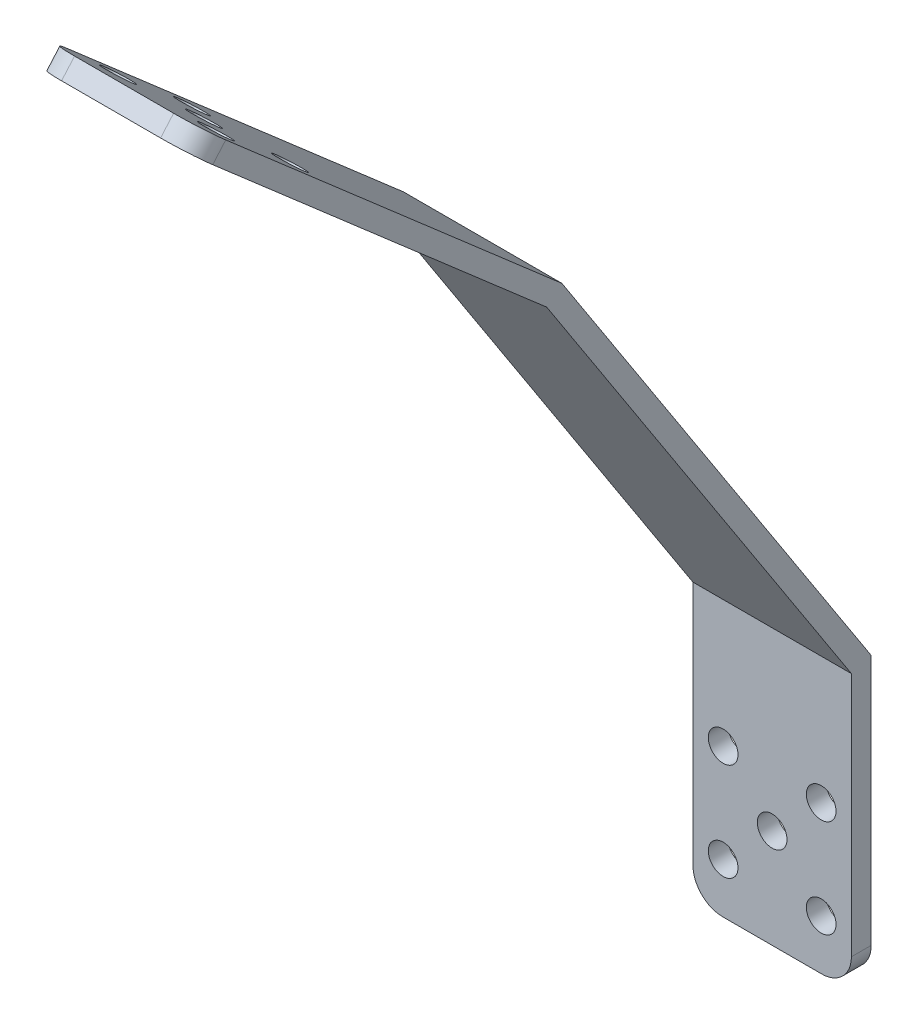
SolidWorks part; units mm, degrees
ref_plane "前视" through (0, 0, 0) normal (0, 0, 1) x (1, 0, 0)
ref_plane "上视" through (0, 0, 0) normal (0, 1, 0) x (1, 0, 0)
ref_plane "右视" through (0, 0, 0) normal (1, 0, 0) x (0, 0, -1)
sketch "草图1" plane through (0, 0, 0) normal (0, 0, 1) x (1, 0, 0)
  line L0 (0, 14.7362) -> (0, -14.2678) construction
  line L1 (-15.916, 0) -> (15.5486, 0) construction
  line L3 (-8, 24) -> (8, 24)
  line L4 (-8, 24) -> (-8, -24)
  line L5 (-8, -24) -> (8, -24)
  line L6 (8, 24) -> (8, -24)
  line L7 (-8, 24) -> (8, -24) construction
  line L8 (-8, -24) -> (8, 24) construction
  point P5 (0, 0)
  dimension "D1" = 16
  dimension "D2" = 48
extrude "凸台-拉伸1" add sketch "草图1" along normal blind 3
sketch "草图2" plane through (0, 0, 3) normal (0, 0, 1) x (1, 0, 0)
  line L0 (-7.7762, 0) -> (8.6691, 0) construction
  line L1 (0, 11.5397) -> (0, -11.8699) construction
  line L2 (-7.9817, -14) -> (8.6691, -14) construction
  line L3 (-8, -24) -> (8, -24) construction
  circle A0 centre (0, -14) radius 7 construction
  circle A1 centre (-4.9497, -9.0503) radius 1.5
  circle A2 centre (0, -14) radius 1.5
  circle A3 centre (4.9497, -9.0503) radius 1.5
  circle A4 centre (4.9497, -18.9497) radius 1.5
  circle A5 centre (-4.9497, -18.9497) radius 1.5
  point P21 (0, -14)
  dimension "D2" = 3
  dimension "D3" = 14
  dimension "D4" = 3
  dimension "D1" = 10
  dimension "D5" = 4
extrude "切除-拉伸1" cut sketch "草图2" against normal through all
ref_plane "基准面1" through (0, 12.1847, -10.592) normal (0, 0.7547, -0.6561) x (-1, 0, 0)
sketch "草图3" plane through (0, 12.1847, -10.592) normal (0, 0.7547, -0.6561) x (-1, 0, 0)
  line L0 (-8, 18.0095) -> (8, 18.0095) construction
  line L1 (-8, 18.0095) -> (8, 18.0095)
  line L2 (0, 34.8976) -> (0, -9.373) construction
  line L3 (-18.8539, 0) -> (18.6715, 0) construction
  line L4 (-8, 18.0095) -> (-8, 106.0095)
  line L5 (-8, 106.0095) -> (8, 106.0095)
  line L6 (8, 106.0095) -> (8, 18.0095)
  dimension "D1" = 88
extrude "凸台-拉伸2" add sketch "草图3" along normal blind 3 separate body
sketch "草图4" plane through (0, 11.8153, 13.592) normal (0, -0.6561, -0.7547) x (-1, 0, 0)
  line L0 (-8, 19.1449) -> (8, 19.1449) construction
  line L1 (-8, 19.1449) -> (-8, 16.1449) construction
  line L2 (-8, 16.1449) -> (8, 16.1449) construction
  line L3 (8, 19.1449) -> (8, 16.1449) construction
  line L4 (-8, 19.1449) -> (8, 19.1449)
  line L5 (-8, 19.1449) -> (-8, 16.1449)
  line L6 (-8, 16.1449) -> (8, 16.1449)
  line L7 (8, 19.1449) -> (8, 16.1449)
extrude "凸台-拉伸3" add sketch "草图4" along normal blind 2
sketch "草图5" plane through (0, 12.1847, -10.592) normal (0, -0.7547, 0.6561) x (1, 0, 0)
  line L0 (0, 80.4499) -> (0, -20.8419) construction
  line L1 (-25.5488, 95.34) -> (29.0902, 95.34) construction
  circle A0 centre (0, 95.34) radius 1.5
  circle A1 centre (0, 95.34) radius 7 construction
  circle A2 centre (-4.9497, 100.2897) radius 1.5
  circle A3 centre (4.9497, 100.2897) radius 1.5
  circle A4 centre (4.9497, 90.3903) radius 1.5
  circle A5 centre (-4.9497, 90.3903) radius 1.5
  point P19 (0, 95.34)
  dimension "D2" = 3
  dimension "D3" = 14
  dimension "D4" = 3
  dimension "D1" = 95.34
  dimension "D5" = 4
extrude "切除-拉伸2" cut sketch "草图5" against normal through all
fillet "圆角3" radius 3 4 edges at (-8, -24, 1.5) (8, -24, 1.5) (8, 82.8653, 68.4304) (-8, 82.8653, 68.4304)
sketch "草图6" plane through (-8, 0, 0) normal (-1, 0, 0) x (0, 0, 1)
  line L0 (33.5315, 50.5406) -> (3, 3.4725)
  line L1 (3, 24) -> (3, -21) construction
  line L3 (31.2445, 52.5276) -> (0, 4.3603)
  line L4 (-0.4776, 24.952) -> (65.1821, 82.0291) construction
  line L5 (0, 24) -> (0, -21) construction
  line L6 (3, 24) -> (67.1503, 79.765) construction
  line L7 (31.2445, 52.5276) -> (33.5315, 50.5406)
  line L8 (0, 4.3603) -> (3, 3.4725)
  dimension "D1" = 3
extrude "凸台-拉伸4" add sketch "草图6" against normal up to surface (16 mm away) up to face at (8, 27.0933, 17.2756)
ref_plane "基准面2" through (-8, 24.952, -0.4776) normal (0, 0.6561, 0.7547) x (1, 0, 0)
sketch "草图9" plane through (8, 0, 0) normal (1, 0, 0) x (0, 0, -1)
  line L0 (0, 4.3603) -> (-31.2445, 52.5276)
  line L1 (0.4776, 24.952) -> (-65.1821, 82.0291) construction
  line L2 (-3, 8.9852) -> (-25.3322, 43.4131) construction
  line L3 (0, -21) -> (0, 24) construction
  line L4 (0, 4.3603) -> (6.0528, 30.6803)
  line L5 (6.0528, 30.6803) -> (-31.2445, 52.5276)
extrude "切除-拉伸3" cut sketch "草图9" against normal through all
sketch "草图11" plane through (-8, 0, 0) normal (-1, 0, 0) x (0, 0, 1)
  line L0 (0, 4.3603) -> (3, 3.4725)
  line L1 (31.2445, 52.5276) -> (33.5315, 50.5406)
  line L2 (76.3463, 89.084) -> (32.7692, 51.203)
  line L3 (32.7692, 51.203) -> (2, 3.7684)
  line L4 (2, 3.7684) -> (2, -26.5916)
  line L5 (2, -26.5916) -> (76.3463, 89.084)
  line L6 (0, 4.3603) -> (0, -21) construction
  line L8 (3, 3.4725) -> (33.5315, 50.5406) construction
  line L10 (33.5315, 50.5406) -> (67.1503, 79.765) construction
  line M8 (0, -21) -> (3, -21)
  line M9 (3, -21) -> (3, 3.4725)
  line M10 (3, 3.4725) -> (33.5315, 50.5406)
  line M11 (33.5315, 50.5406) -> (67.1503, 79.765)
  line M12 (67.1503, 79.765) -> (65.1821, 82.0291)
  dimension "D1" = 2
extrude "切除-拉伸4" cut sketch "草图11" against normal through all contours L4 L5 L2 M12 M11 M10 M9 M8 | L2 L1 M12 M11 | L1 L3 L0 M10 | L0 L4 M8 M9 region at (-8, 27.2464, 17.8246) region at (-8, -8.6896, 2.499) region at (-8, 29.1159, 30.0083) region at (-8, 65.5073, 49.9861)
sketch "草图12" plane through (0, 1.2913, -1.9907) normal (0, 0.5442, -0.839) x (-1, 0, 0)
  line L0 (8, 61.0716) -> (8, 3.6581) construction
  line L1 (-6, 59.0716) -> (6, 59.0716)
  line L2 (-6, 59.0716) -> (-6, 5.6581) construction
  line L3 (-6, 5.6581) -> (6, 5.6581)
  line L4 (6, 59.0716) -> (6, 5.6581) construction
  line L5 (-8, 3.6581) -> (-8, 61.0716) construction
  line L6 (8, 61.0716) -> (-8, 61.0716) construction
  line L7 (8, 3.6581) -> (-8, 3.6581) construction
  line L8 (-6, 53.4147) -> (6, 41.4147)
  line L9 (6, 41.4147) -> (6, 47.0716)
  line L10 (6, 47.0716) -> (-6, 59.0716)
  line L11 (-6, 59.0716) -> (-6, 53.4147)
  line L12 (-6, 17.6581) -> (6, 5.6581)
  line L13 (6, 5.6581) -> (6, 11.3149)
  line L14 (6, 11.3149) -> (-6, 23.3149)
  line L15 (-6, 23.3149) -> (-6, 17.6581)
  line L16 (-6, 35.5364) -> (6, 23.5364)
  line L17 (6, 23.5364) -> (6, 29.1933)
  line L18 (6, 29.1933) -> (-6, 41.1933)
  line L19 (-6, 41.1933) -> (-6, 35.5364)
  line L20 (-6, 32.3648) -> (6, 32.3648)
  line L21 (-6, 35.5364) -> (-6, 32.3648)
  line L22 (6, 29.1933) -> (6, 32.3648)
  dimension "D1" = 2
  dimension "D2" = 2
  dimension "D3" = 2
  dimension "D4" = 2
  dimension "D5" = 4
  dimension "D6" = 45
  dimension "D7" = 4
  dimension "D8" = 4
extrude "切除-拉伸5" [suppressed] cut sketch "草图12" against normal through all contours L14 L15 L12 L13 | L20 L16 L17 L18 | L10 L11 L8 L9 | L16 L17 L18 L19
fillet "圆角4" [suppressed] radius 1
